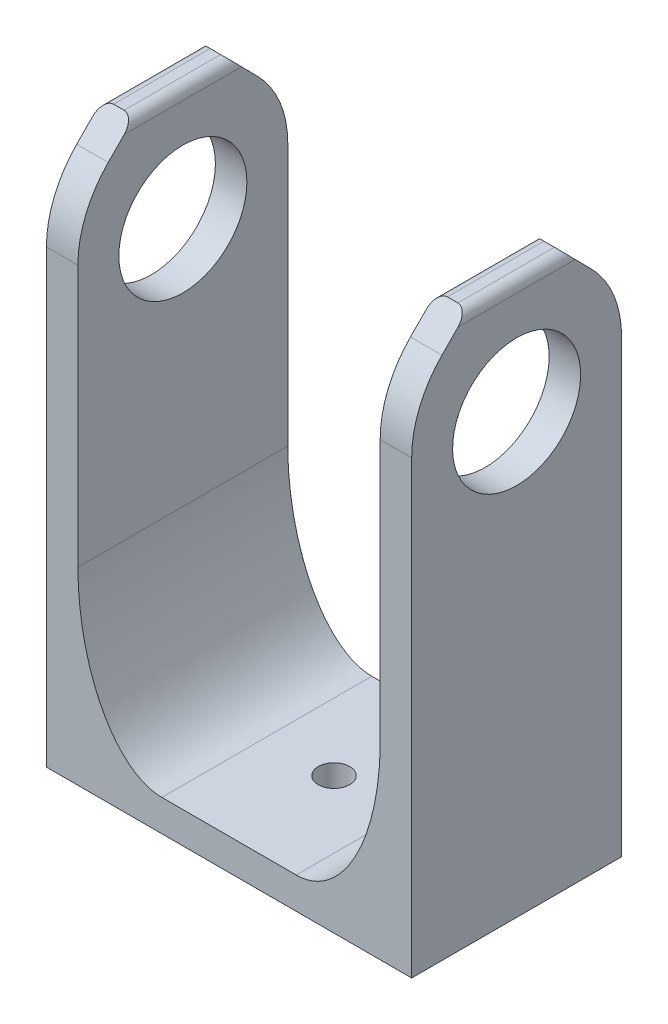
SolidWorks part; units mm, degrees
ref_plane "前视基准面" through (0, 0, 0) normal (0, 0, 1) x (1, 0, 0)
ref_plane "上视基准面" through (0, 0, 0) normal (0, 1, 0) x (1, 0, 0)
ref_plane "右视基准面" through (0, 0, 0) normal (1, 0, 0) x (0, 0, -1)
sketch "草图1" plane through (0, 0, 0) normal (0, 0, 1) x (1, 0, 0)
  line L0 (-18.0339, 1.3314) -> (-18.0339, -31.1835)
  line L1 (-18.0339, -31.1835) -> (16.7661, -31.1835)
  line L2 (16.7661, -31.1835) -> (16.7661, 20.3165)
  line L3 (15.7661, 21.3165) -> (14.7661, 21.3165)
  line L4 (13.7661, 20.3165) -> (13.7661, -23.2767)
  line L5 (9.0896, -28.1835) -> (-9.5778, -28.1835)
  line L6 (-15.0339, -10.2767) -> (-15.0339, 20.3165)
  line L7 (-16.0339, 21.3165) -> (-17.0339, 21.3165)
  line L8 (-18.0339, 20.3165) -> (-18.0339, 1.3314)
  line L9 (-15.0339, -10.2767) -> (-15.0339, -23.5103)
  line L10 (-15.0339, -23.5103) -> (-15.0339, -28.1835)
  line L11 (-15.0339, -28.1835) -> (-9.5778, -28.1835)
  line L12 (13.7661, -23.2767) -> (13.7661, -28.1835)
  line L13 (13.7661, -28.1835) -> (9.0896, -28.1835)
  arc A2 (14.7661, 21.3165) -> (13.7661, 20.3165) centre (14.7661, 20.3165) ccw
  arc A3 (16.7661, 20.3165) -> (15.7661, 21.3165) centre (15.7661, 20.3165) ccw
  arc A4 (-17.0339, 21.3165) -> (-18.0339, 20.3165) centre (-17.0339, 20.3165) ccw
  arc A5 (-15.0339, 20.3165) -> (-16.0339, 21.3165) centre (-16.0339, 20.3165) ccw
  point P15 (9.9661, 34.5437)
  point P18 (13.9661, 34.5437)
  dimension "D1" = 1
  dimension "D2" = 3
  dimension "D3" = 3
  dimension "D4" = 3
  dimension "D5" = 52.5
  dimension "D6" = 52.5
  dimension "D7" = 28.8
extrude "凸台-拉伸1" add sketch "草图1" along normal blind 20
sketch "草图2" plane through (16.7661, 0, 0) normal (1, 0, 0) x (0, 0, -1)
  line L0 (0, -31.1835) -> (0, 20.3165) construction
  line L1 (-20, 21.3165) -> (0, 21.3165) construction
  line L2 (-10, 16.5437) -> (-20, 16.5437) construction
  line L3 (-20, -31.1835) -> (-20, 20.3165) construction
  line L4 (-10, 16.5437) -> (-10, 10.5437) construction
  line L5 (-10, 10.5437) -> (-5.1413, 10.5437) construction
  line L8 (0, 15.8474) -> (-5.4027, 21.3165)
  line L12 (-5.4027, 21.3165) -> (0, 21.3165)
  line L13 (0, 21.3165) -> (0, 15.8474)
  line L15 (-20, 15.8474) -> (-14.5973, 21.3165)
  line L16 (-20, 21.3165) -> (-20, 15.8474)
  line L17 (-14.5973, 21.3165) -> (-20, 21.3165)
  circle A0 centre (-10, 10.5437) radius 6.1
  dimension "D3" = 12.2
  dimension "D2" = 6
extrude "切除-拉伸1" cut sketch "草图2" against normal up to surface (34.8 mm away) up to face at (-18.0339, -5.4335, 10)
sketch "草图3" plane through (0, -31.1835, 0) normal (0, -1, 0) x (1, 0, 0)
  line L0 (-0.6339, 20) -> (-0.6339, 10) construction
  line L1 (-18.0339, 20) -> (16.7661, 20) construction
  line L2 (-0.6339, 10) -> (3.3661, 10) construction
  circle A0 centre (-0.6339, 10) radius 1.5
  dimension "D1" = 3
  dimension "D2" = 4
extrude "切除-拉伸2" cut sketch "草图3" against normal up to surface (52.5 mm away) up to face at (-16.5339, 21.3165, 10)
fillet "圆角1" radius 10 4 edges at (-16.5339, 15.8474, 20) (-16.5339, 15.8474, 0) (15.2661, 15.8474, 20) (15.2661, 15.8474, 0)
fillet "圆角2" radius 8 1 edges at (-15.0339, -28.1835, 10) second distance 15 first distance on face at (-0.6339, -28.1835, 8.5)
fillet "圆角3" radius 8 1 edges at (13.7661, -28.1835, 10) second distance 15 first distance on face at (-0.6339, -28.1835, 8.5)
